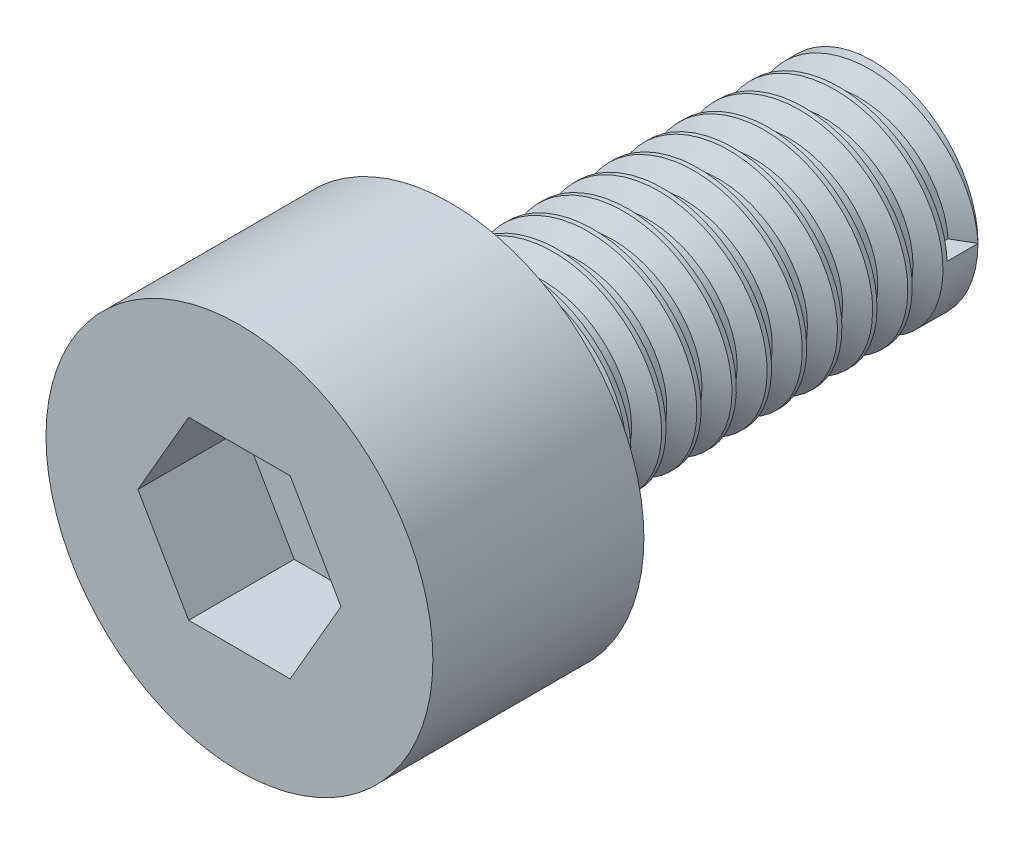
SolidWorks part; units mm, degrees
ref_plane "前视基准面" through (0, 0, 0) normal (0, 0, 1) x (1, 0, 0)
ref_plane "上视基准面" through (0, 0, 0) normal (0, 1, 0) x (1, 0, 0)
ref_plane "右视基准面" through (0, 0, 0) normal (1, 0, 0) x (0, 0, -1)
sketch "草图1" plane through (0, 0, 0) normal (0, 0, 1) x (1, 0, 0)
  circle A0 centre (0, 0) radius 1.5
  dimension "diameter" = 3
extrude "螺杆_直径3_长度10" add sketch "草图1" along normal blind 6
thread "真实螺纹_M3x0.5_右旋_长10" pitch 0.5 method cut profile "螺纹线轮廓1" start angle 0, offset 0, length 6, pitch 0.5, diameter 3
ref_plane "基准面4" through (1.5, 0, 0) normal (0, -1, 0) x (1, 0, 0)
sketch "螺纹线轮廓1" plane through (1.5, 0, 0) normal (0, -1, 0) x (1, 0, 0)
  line L0 (0, 0) -> (0, 0.5) construction
  line L11 (0, 0) -> (0, 0.4375)
  line L12 (0, 0.4375) -> (-0.2706, 0.2812)
  line L13 (-0.2706, 0.2812) -> (-0.2706, 0.1562)
  line L15 (-0.2706, 0.1562) -> (0, 0)
  line L17 (-0.2706, 0.2187) -> (0, 0.2187) construction
  point P2 (0, 0)
  dimension "Pitch" = 0.5
  dimension "Profile_Angle" = 60
  dimension "Profile_Land" = 0.125
  dimension "Profile_Height" = 0.2706
sketch "草图2" plane through (0, 0, 6) normal (0, 0, 1) x (1, 0, 0)
  circle A0 centre (0, 0) radius 2.75
  dimension "diameter" = 5.5
extrude "杯头_直径5.5_厚度3" add sketch "草图2" along normal blind 3
sketch "草图3" plane through (0, 0, 9) normal (0, 0, 1) x (1, 0, 0)
  line L0 (1.4434, 0) -> (0.7217, 1.25)
  line L1 (0.7217, 1.25) -> (-0.7217, 1.25)
  line L2 (-0.7217, 1.25) -> (-1.4434, 0)
  line L3 (-1.4434, 0) -> (-0.7217, -1.25)
  line L4 (-0.7217, -1.25) -> (0.7217, -1.25)
  line L5 (0.7217, -1.25) -> (1.4434, 0)
  dimension "x0" = 1.4434
  dimension "x1" = 0.7217
  dimension "x2" = 0.7217
  dimension "x3" = 1.4434
  dimension "x4" = 0.7217
  dimension "x5" = 0.7217
  dimension "y1" = 1.25
  dimension "y4" = 1.25
extrude "内六角_对边2.5_深1.5" cut sketch "草图3" against normal blind 1.5
